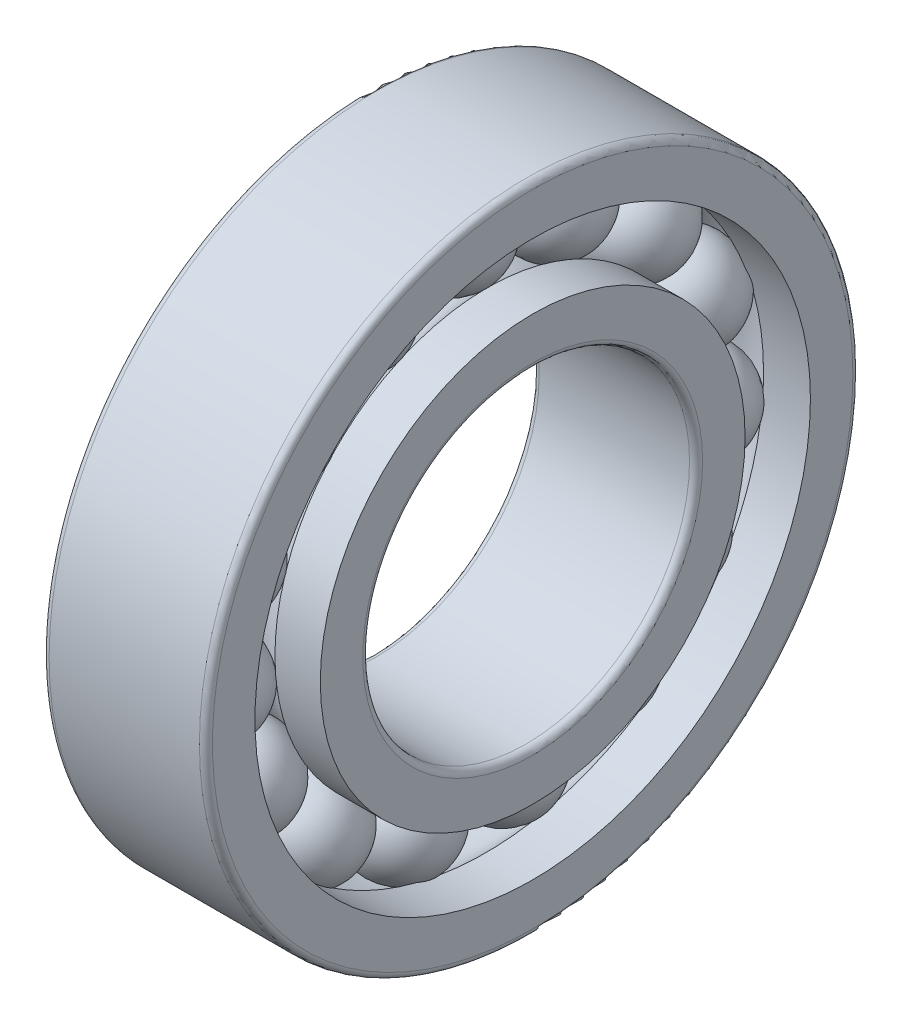
SolidWorks part; units mm, degrees
ref_plane "Plane1" through (0, 0, 0) normal (0, 0, 1) x (1, 0, 0)
ref_plane "Plane2" through (0, 0, 0) normal (0, 1, 0) x (1, 0, 0)
ref_plane "Plane3" through (0, 0, 0) normal (1, 0, 0) x (0, 0, -1)
sketch "Clipboard" plane through (0, 0, 0) normal (0, 0, 1) x (1, 0, 0)
  line L0 (-10, 0) -> (10, 0) construction
  line L1 (0, 0) -> (21.5988, -5.7874)
  line L2 (0, 0) -> (4.7618, -0.0831)
  line L3 (0, 0) -> (22.3573, 0.3902)
  line L4 (0, 0) -> (-22.3573, -0.3902)
  dimension "BallCLRad" = 4.7625
sketch "CagSpiSke" plane through (0, 0, 0) normal (0, 0, 1) x (1, 0, 0)
  line L0 (0.0952, 4.6038) -> (0.0953, 4.9213)
  line L1 (0.0953, 4.9213) -> (-0.0953, 4.9213)
  line L2 (-0.0953, 4.9213) -> (-0.0952, 4.6038)
  line L3 (-0.0952, 4.6038) -> (0.0952, 4.6038)
  line L4 (-20.6375, 0) -> (20.6375, 0) construction
  line L5 (0, 0) -> (0, 23.7692) construction
  dimension "OD" = 9.8425
  dimension "ID" = 9.2075
revolve "CageSpine" add sketch "CagSpiSke" angle 0.001 about L4 reverse direction yes
ref_axis "Axis1" through (-50, 0, 0) along (1, 0, 0)
sketch "CagBalSke" plane through (0, 0, 0) normal (0, 0, 1) x (1, 0, 0)
  line L0 (-1.0478, 4.7625) -> (1.0478, 4.7625)
  line L1 (-1.905, 4.7625) -> (1.905, 4.7625) construction
  line L2 (-10, 0) -> (10, 0) construction
  line L3 (0, 0) -> (0, 24) construction
  arc A0 (1.0478, 4.7625) -> (-1.0478, 4.7625) centre (0, 4.7625) cw
  dimension "BallCLRad" = 4.7625
revolve "CageBall" [suppressed] add sketch "CagBalSke" angle 360 about L1 reverse direction yes
pattern_circular "CageBalls" [suppressed] count 15 every 24 about axis through (-50, 0, 0) along (1, 0, 0)
sketch "CagTrmODSke" plane through (0, 0, 0) normal (0, 0, 1) x (1, 0, 0)
  line L0 (1.0488, 4.9212) -> (1.0488, 5.8113)
  line L1 (1.0488, 5.8113) -> (-1.0488, 5.8113)
  line L2 (-1.0488, 5.8113) -> (-1.0488, 4.9212)
  line L3 (-1.0488, 4.9212) -> (1.0488, 4.9212)
  line L4 (-20.6375, 0) -> (20.6375, 0) construction
  line L5 (0, 0) -> (0, 25) construction
  dimension "Width" = 2.0975
  dimension "ID" = 9.8425
  dimension "OD" = 11.6225
revolve "CageTrimOD" [suppressed] cut sketch "CagTrmODSke" angle 360 about L4 reverse direction yes
sketch "CagTrmIDSke" plane through (0, 0, 0) normal (0, 0, 1) x (1, 0, 0)
  line L0 (1.0487, 3.7158) -> (1.0488, 4.6037)
  line L1 (1.0488, 4.6037) -> (-1.0488, 4.6037)
  line L2 (-1.0488, 4.6037) -> (-1.0487, 3.7158)
  line L3 (-1.0487, 3.7158) -> (1.0487, 3.7158)
  line L4 (-20.6375, 0) -> (20.6375, 0) construction
  line L5 (0, 0) -> (0, 25) construction
  dimension "Width" = 2.0975
  dimension "ID" = 7.4315
  dimension "OD" = 9.2075
revolve "CageTrimID" [suppressed] cut sketch "CagTrmIDSke" angle 360 about L4 reverse direction yes
sketch "BalSimSke" plane through (0, 0, 0) normal (0, 0, 1) x (1, 0, 0)
  line L0 (-10, 0) -> (10, 0) construction
  line L1 (-10, 4.7625) -> (10, 4.7625) construction
  line L2 (0, 0) -> (0, 23) construction
  circle A0 centre (0, 4.7625) radius 0.9525
  dimension "BallCLRad" = 4.7625
  dimension "Ball_diameter" = 1.905
revolve "BallsSimplified" [suppressed] add sketch "BalSimSke" angle 360 about L0
sketch "BalDetSke" plane through (0, 0, 0) normal (0, 0, 1) x (1, 0, 0)
  line L0 (-0.9525, 4.7625) -> (0.9525, 4.7625)
  line L1 (-1.905, 4.7625) -> (1.905, 4.7625) construction
  line L2 (0, 0) -> (0, 25) construction
  arc A0 (0.9525, 4.7625) -> (-0.9525, 4.7625) centre (0, 4.7625) cw
  dimension "BallCLRad" = 4.7625
  dimension "Ball_diameter" = 1.905
revolve "BallDetailed" add sketch "BalDetSke" angle 360 about L1 reverse direction yes
sketch "InnRacSke" plane through (0, 0, 0) normal (0, 0, 1) x (1, 0, 0)
  line L0 (-0.646, 4.1275) -> (-1.5875, 4.1275)
  line L1 (-1.5875, 4.1275) -> (-1.5875, 3.302)
  line L2 (-1.4605, 3.175) -> (1.4605, 3.175)
  line L3 (1.5875, 3.302) -> (1.5875, 4.1275)
  line L4 (1.5875, 4.1275) -> (0.706, 4.1275)
  line L5 (-20.6375, 0) -> (20.6375, 0) construction
  line L6 (0, 0) -> (0, 30) construction
  arc A0 (-1.5875, 3.302) -> (-1.4605, 3.175) centre (-1.4605, 3.302) ccw
  arc A1 (1.4605, 3.175) -> (1.5875, 3.302) centre (1.4605, 3.302) ccw
  arc A2 (0.706, 4.1275) -> (-0.646, 4.1275) centre (0.03, 4.7625) cw
  dimension "BallCLRad" = 4.7625
  dimension "Fillet_radius" = 0.127
  dimension "Ball_diameter" = 1.855
  dimension "ID" = 6.35
  dimension "OD" = 8.255
  dimension "Width" = 3.175
revolve "InnerRace" add sketch "InnRacSke" angle 360 about L5 reverse direction yes
sketch "OutRacSke" plane through (0, 0, 0) normal (0, 0, 1) x (1, 0, 0)
  line L0 (-0.676, 5.3975) -> (-1.5875, 5.3975)
  line L1 (-1.5875, 5.3975) -> (-1.5875, 6.223)
  line L2 (-1.4605, 6.35) -> (1.4605, 6.35)
  line L3 (1.5875, 6.223) -> (1.5875, 5.3975)
  line L4 (1.5875, 5.3975) -> (0.676, 5.3975)
  line L5 (-20.6375, 0) -> (20.6375, 0) construction
  line L6 (0, 0) -> (0, 30) construction
  arc A0 (-1.5875, 6.223) -> (-1.4605, 6.35) centre (-1.4605, 6.223) cw
  arc A1 (1.4605, 6.35) -> (1.5875, 6.223) centre (1.4605, 6.223) cw
  arc A2 (0.676, 5.3975) -> (-0.676, 5.3975) centre (0, 4.7625) ccw
  dimension "BallCLRad" = 4.7625
  dimension "Fillet_radius" = 0.127
  dimension "Ball_diameter" = 1.855
  dimension "Width" = 3.175
revolve "OuterRace" add sketch "OutRacSke" angle 360 about L5 reverse direction yes
pattern_circular "BallsDetailed" count 15 every 24 about axis through (-50, 0, 0) along (1, 0, 0) of "BallDetailed"
equation "\"BallCLRad@Clipboard\" = ( \"OD@OutRacSke\" + \"ID@InnRacSke\" ) / 4"
equation "\"BallCLRad@BalSimSke\" = \"BallCLRad@Clipboard\""
equation "\"BallCLRad@BalDetSke\" = \"BallCLRad@Clipboard\""
equation "\"BallCLRad@InnRacSke\" = \"BallCLRad@Clipboard\""
equation "\"BallCLRad@OutRacSke\" = \"BallCLRad@Clipboard\""
equation "\"Ball_diameter@InnRacSke\" = \"Ball_diameter@BalDetSke\" - 0.05"
equation "\"Ball_diameter@OutRacSke\" = \"Ball_diameter@BalDetSke\" - 0.05"
equation "\"Ball_diameter@BalSimSke\" = \"Ball_diameter@BalDetSke\""
equation "\"Width@OutRacSke\" = \"Width@InnRacSke\""
equation "\"Fillet_radius@OutRacSke\" = \"Fillet_radius@InnRacSke\""
equation "\"Max_count@Clipboard\" = int( 3.14159265 / atn(( \"Ball_diameter@BalDetSke\" / 2) / sqr( \"BallCLRad@Clipboard\"  *  \"BallCLRad@Clipboard\" - ( \"Ball_diameter@BalDetSke\" / 2) *  ( \"Ball_diameter@BalDetSke\" / 2))))"
equation "\"Max_count@Clipboard\" = ((sgn( \"Max_count@Clipboard\" - \"Count@Clipboard\" )-1)*( \"Max_count@Clipboard\" - \"Count@Clipboard\" ))/-2+ \"Count@Clipboard\""
equation "\"Count@BallsDetailed\" = int( \"Show_count@Clipboard\" ) "
equation "\"Count@BallsDetailed\" = ((sgn( \"Count@BallsDetailed\" - \"Max_count@Clipboard\" )-1)*( \"Count@BallsDetailed\" - \"Max_count@Clipboard\" ))/-2+ \"Max_count@Clipboard\""
equation "\"Count@BallsDetailed\" = ((sgn( \"Count@BallsDetailed\" - \"Min_count@Clipboard\" )+1)*( \"Count@BallsDetailed\" - \"Min_count@Clipboard\"))/2 +\"Min_count@Clipboard\""
equation "\"Angle@BallsDetailed\" = 360.0 / \"Max_count@Clipboard\""
equation "\"BallCLRad@CagBalSke\" = \"BallCLRad@Clipboard\""
equation "\"Count@CageBalls\" = \"Count@BallsDetailed\""
equation "\"Angle@CageBalls\" = \"Angle@BallsDetailed\""
equation "\"Angle@CageSpine\" =  \"Angle@CageBalls\" * ( \"Count@CageBalls\" -1 + int( \"Count@CageBalls\" / \"Max_count@Clipboard\" ) )  + 0.001 -  int( \"Count@CageBalls\" / \"Max_count@Clipboard\" ) * 0.001"
equation "\"Angle@CageSpine\" =  \"Angle@CageSpine\" * int( \"Min_count@Clipboard\" / 2) + int(1 / \"Min_count@Clipboard\")  * 0.001"
equation "\"CageWallOD@CagBalSke\" =  \"Ball_diameter@BalDetSke\" * 1.1"
equation "\"Thickness@CagSpiSke\" =  \"Ball_diameter@BalDetSke\" * 0.1"
equation "\"OD@CagTrmODSke\" = \"BallCLRad@Clipboard\" * 2 + \"CageWallOD@CagBalSke\" + 0.002"
equation "\"ID@CagTrmODSke\" = \"BallCLRad@Clipboard\" * 2 + \"Ball_diameter@BalDetSke\" / 6"
equation "\"OD@CagTrmIDSke\" = \"BallCLRad@Clipboard\" * 2 - \"Ball_diameter@BalDetSke\" / 6"
equation "\"ID@CagTrmIDSke\" = \"BallCLRad@Clipboard\" * 2 - \"CageWallOD@CagBalSke\" + 0.002"
equation "\"OD@CagSpiSke\" = \"ID@CagTrmODSke\""
equation "\"ID@CagSpiSke\" = \"OD@CagTrmIDSke\""
equation "\"Width@CagTrmODSke\" = \"CageWallOD@CagBalSke\" + 0.002"
equation "\"Width@CagTrmIDSke\" = \"CageWallOD@CagBalSke\" + 0.002"
